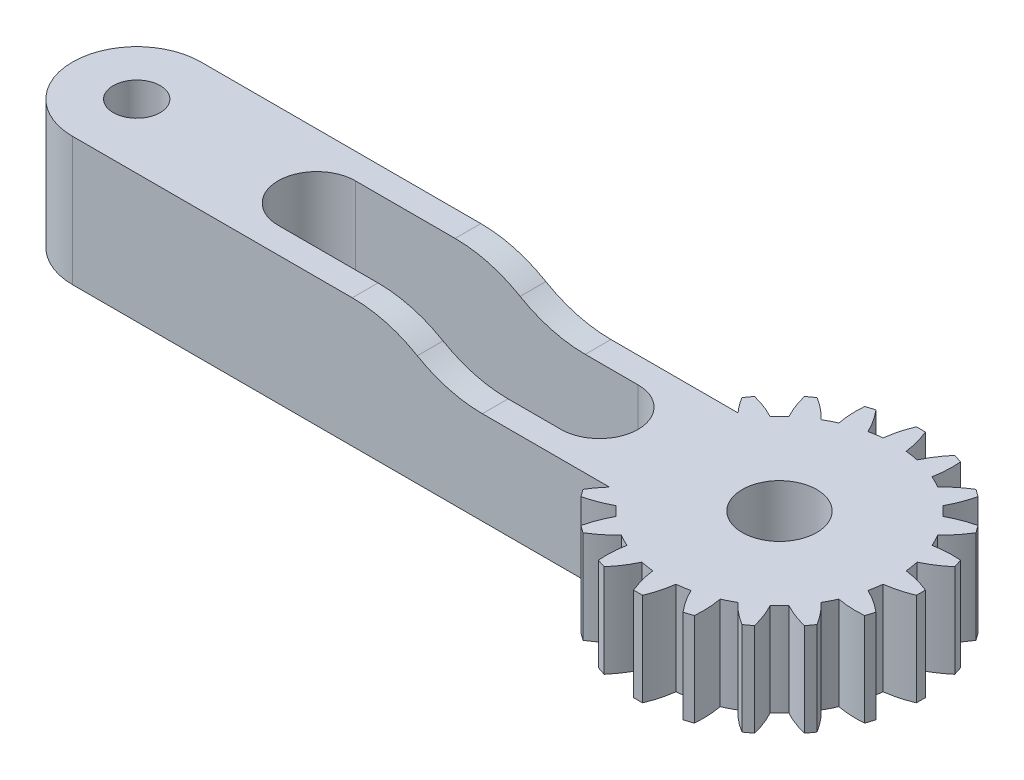
SolidWorks part; units mm, degrees
material "ABS"
ref_plane "Ebene vorne" through (0, 0, 0) normal (0, 0, 1) x (1, 0, 0)
ref_plane "Ebene oben" through (0, 0, 0) normal (0, 1, 0) x (1, 0, 0)
ref_plane "Ebene rechts" through (0, 0, 0) normal (1, 0, 0) x (0, 0, -1)
sketch "Skizze2" plane through (0, 0, 0) normal (0, 1, 0) x (1, 0, 0)
  line L0 (-25, 5) -> (25, 5)
  line L1 (0, 0) -> (0, 16.3031) construction
  line L2 (0, 0) -> (-44.1058, 0) construction
  line L3 (-25, -5) -> (25, -5)
  arc A0 (-25, -5) -> (-25, 5) centre (-25, 0) cw
  arc A1 (25, -5) -> (25, 5) centre (25, 0) ccw
  circle A2 centre (-25, 0) radius 1.825
  circle A3 centre (25, 0) radius 2.9
  point P4 (0, 5)
  point P12 (0, -5)
  dimension "D3" = 3.65
  dimension "D4" = 5.8
  dimension "D1" = 5
  dimension "D2" = 50
extrude "Aufsatz-Linear austragen1" add sketch "Skizze2" along normal blind 10
sketch "Skizze4" plane through (0, 10, 0) normal (0, 1, 0) x (1, 0, 0)
  line L0 (25, 5) -> (0, 5)
  line L1 (25, 5) -> (-25, 5) construction
  line L2 (0, 5) -> (0, -5)
  line L3 (-25, -5) -> (25, -5) construction
  line L4 (0, -5) -> (25, -5)
  arc A0 (25, 5) -> (25, -5) centre (25, 0) cw
  arc A1 (25, -5) -> (25, 5) centre (25, 0) ccw construction
extrude "Schnitt-Linear austragen1" cut sketch "Skizze4" against normal blind 2.75
fillet "Verrundung1" radius 10 1 edges at (0, 7.25, 0)
fillet "Verrundung2" radius 10 1 edges at (0, 10, 0)
sketch "Skizze5" plane through (0, 7.25, 0) normal (0, 1, 0) x (1, 0, 0)
  circle A0 centre (25, 0) radius 5
  arc A1 (25, -5) -> (25, 5) centre (25, 0) ccw construction
  circle A2 centre (25, 0) radius 9
  dimension "D1" = 18
extrude "Aufsatz-Linear austragen2" add sketch "Skizze5" against normal up to surface (7.25 mm away) up to face at (25, 0, 2.9)
sketch "Skizze6" plane through (0, 7.25, 0) normal (0, 1, 0) x (1, 0, 0)
  line L0 (25, 0) -> (35.1018, 0) construction
  line L1 (36, -0.35) -> (36, 0.35)
  arc A0 (33.9549, -0.9) -> (36, -0.35) centre (32.9268, 7) ccw
  circle A2 centre (25, 0) radius 2.9 construction
  arc A3 (33.9549, 0.9) -> (33.9549, -0.9) centre (25, 0) cw
  arc A4 (17.5167, -5) -> (17.5167, 5) centre (25, 0) ccw construction
  arc A5 (33.9549, 0.9) -> (36, 0.35) centre (32.9268, -7) cw
  point P6 (36, 0)
  point P10 (34, 0)
  dimension "D1" = 2
  dimension "D2" = 1.8
  dimension "D3" = 0.7
  dimension "D4" = 7
extrude "Aufsatz-Linear austragen3" add sketch "Skizze6" against normal up to surface (7.25 mm away) up to face at (-0.8708, 0, 0)
pattern_circular "Kreismuster1" count 20 over 360 about axis through (25, 7.25, 0) along (0, 1, 0) of "Aufsatz-Linear austragen3"
sketch "Skizze7" plane through (0, 0, -5) normal (0, 0, -1) x (-1, 0, 0)
  line L0 (-8.4507, 2.7562) -> (17.6204, 2.7562) construction
  text T0 "6-DOFRA" font "Century Gothic" height 4
extrude "Schnitt-Linear austragen2" [suppressed] cut sketch "Skizze7" against normal blind 0.25
sketch "Skizze9" plane through (0, 0, 0) normal (0, -1, 0) x (1, 0, 0)
  line L0 (-11, 0) -> (11, 0) construction
  line L1 (-11, 3) -> (11, 3)
  line L2 (-11, -3) -> (11, -3)
  arc A0 (-11, 3) -> (-11, -3) centre (-11, 0) ccw
  arc A1 (11, -3) -> (11, 3) centre (11, 0) ccw
  point P3 (0, 0)
  dimension "D1" = 6
  dimension "D2" = 22
extrude "Schnitt-Linear austragen3" cut sketch "Skizze9" against normal through all
